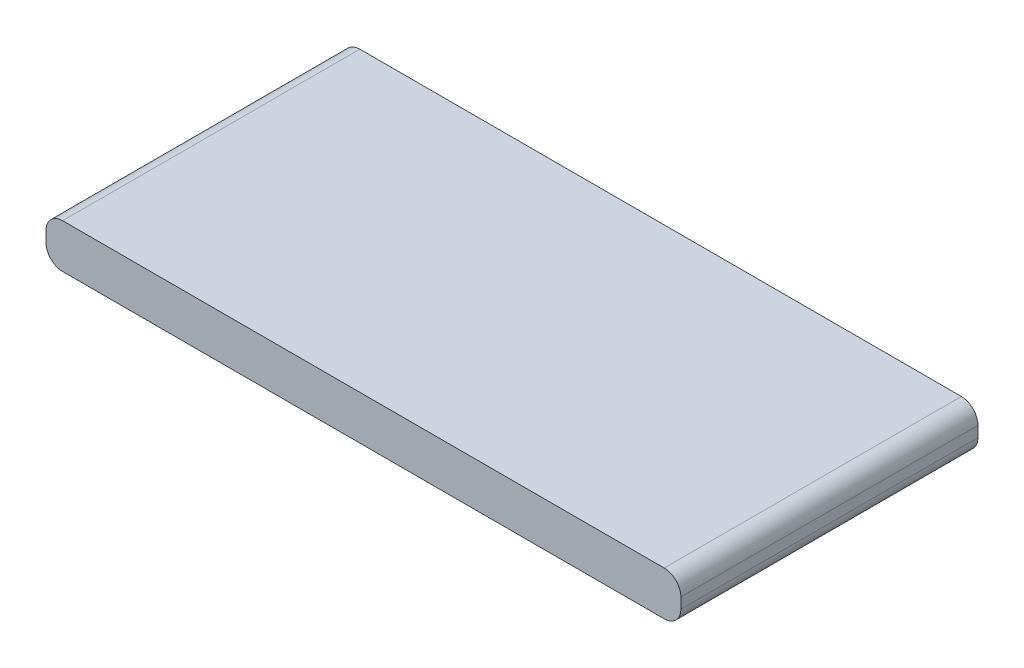
SolidWorks part; units mm, degrees
material "ABS"
ref_plane "X-Y Datum" through (0, 0, 0) normal (0, 0, 1) x (1, 0, 0)
ref_plane "X-Z Datum" through (0, 0, 0) normal (0, 1, 0) x (1, 0, 0)
ref_plane "Y-Z Datum" through (0, 0, 0) normal (1, 0, 0) x (0, 0, -1)
sketch "Sketch2" plane through (0, 0, 0) normal (0, 0, 1) x (1, 0, 0)
  line L6 (114.3, 7.9241) -> (0, 7.9241)
  line L7 (114.3, 7.9241) -> (114.3, 0)
  line L8 (114.3, 0) -> (0, 0)
  line L9 (0, 7.9241) -> (0, 0)
  dimension "D1" = 114.3
extrude "Boss-Extrude1" add sketch "Sketch2" along normal blind 53.5
fillet "Fillet1" radius 3 4 edges at (114.3, 7.9241, 26.75) (114.3, 0, 26.75) (0, 7.9241, 26.75) (0, 0, 26.75)
